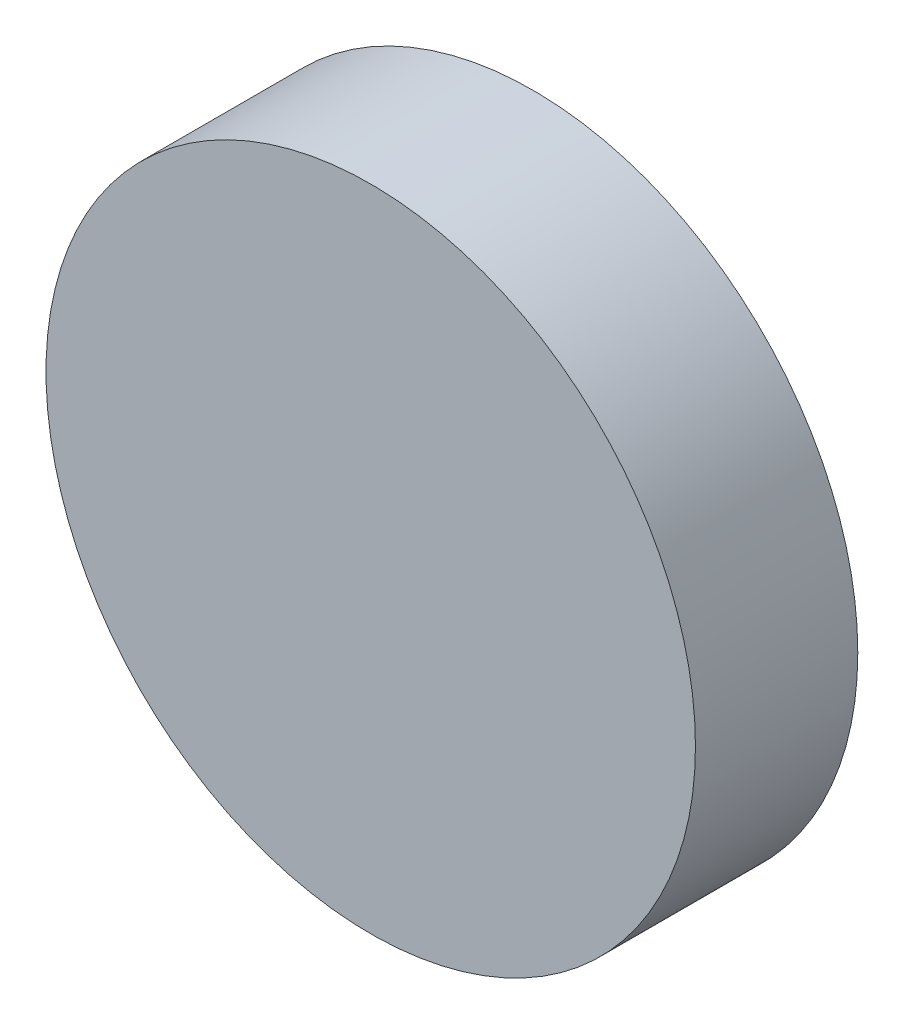
SolidWorks part; units mm, degrees
ref_plane "Front Plane" through (0, 0, 0) normal (0, 0, 1) x (1, 0, 0)
ref_plane "Top Plane" through (0, 0, 0) normal (0, 1, 0) x (1, 0, 0)
ref_plane "Right Plane" through (0, 0, 0) normal (1, 0, 0) x (0, 0, -1)
sketch "Sketch1" plane through (0, 0, 0) normal (0, 0, 1) x (1, 0, 0)
  circle A0 centre (0, 0) radius 6.35
  dimension "D1" = 12.7
extrude "Boss-Extrude1" add sketch "Sketch1" along normal blind 2.54
extrude "Boss-Extrude2" add sketch "Sketch1<2>" along normal blind 3.175
sketch "Sketch1<2>" plane through (0, 0, 0) normal (0, 0, 1) x (1, 0, 0) same geometry as "Sketch1"
